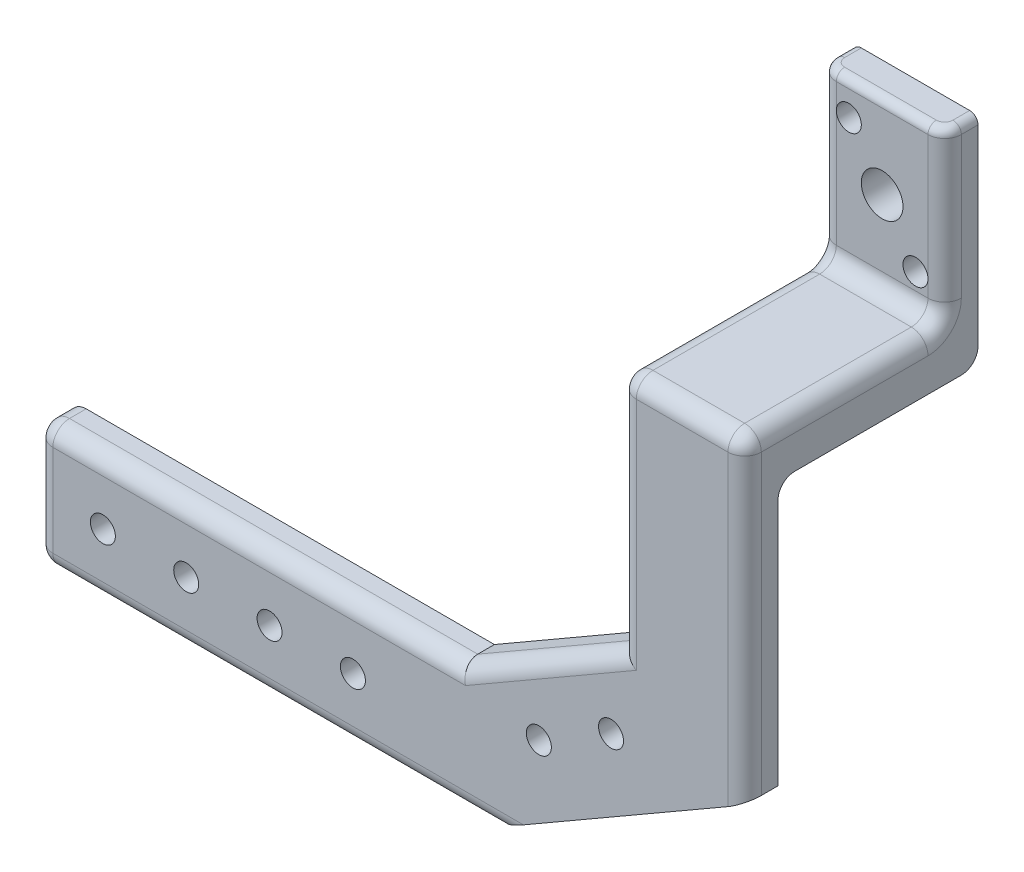
SolidWorks part; units mm, degrees
ref_plane "前视基准面" through (0, 0, 0) normal (0, 0, 1) x (1, 0, 0)
ref_plane "上视基准面" through (0, 0, 0) normal (0, 1, 0) x (1, 0, 0)
ref_plane "右视基准面" through (0, 0, 0) normal (1, 0, 0) x (0, 0, -1)
sketch "草图1" plane through (0, 0, 0) normal (0, 0, 1) x (1, 0, 0)
  line L0 (-7.5, 10) -> (-7.5, -16)
  line L3 (-7.5, 10) -> (7.5, 10)
  line L5 (0, 10) -> (0, -10) construction
  line L6 (-2.5, 0) -> (2.5, 0) construction
  line L9 (-7.5, -16) -> (7.5, -16)
  line L11 (7.5, 10) -> (7.5, -16)
  circle A0 centre (0, 0) radius 2.5
  circle A1 centre (-4, 6) radius 1.5
  circle A2 centre (4, -6) radius 1.5
  point P0 (0, 0)
  dimension "D3" = 5
  dimension "D4" = 3
  dimension "D5" = 3
  dimension "D1" = 26
  dimension "D2" = 15
  dimension "D6" = 4
  dimension "D7" = 4
  dimension "D8" = 6
  dimension "D9" = 6
  dimension "D10" = 15
  dimension "D11" = 10
extrude "凸台-拉伸1" add sketch "草图1" along normal blind 4
sketch "草图14" plane through (0, 0, 4) normal (0, 0, 1) x (1, 0, 0)
  line L1 (-7.5, -16) -> (7.5, -16)
  line L2 (-7.5, -16) -> (-7.5, -10)
  line L3 (-7.5, -10) -> (7.5, -10)
  line L4 (7.5, -16) -> (7.5, -10)
  dimension "D1" = 6
extrude "凸台-拉伸4" add sketch "草图14" along normal blind 20
sketch "草图15" plane through (0, 0, 24) normal (0, 0, 1) x (1, 0, 0)
  line L0 (-7.5, -10) -> (-7.5, -39.0188)
  line L1 (-7.5, -39.0188) -> (-26.52, -50)
  line L2 (-26.52, -50) -> (-77.5, -50)
  line L5 (-77.5, -50) -> (-77.5, -65)
  line L6 (-77.5, -65) -> (-22.5, -65)
  line L8 (-22.5, -65) -> (7.5, -47.6795)
  line L9 (7.5, -47.6795) -> (7.5, -10)
  line L10 (7.5, -10) -> (-7.5, -10)
  line L11 (-7.5, -10) -> (-7.5, -16) construction
  dimension "D1" = 55
  dimension "D2" = 15
  dimension "D3" = 85
  dimension "D4" = 150
  dimension "D5" = 150
  dimension "D6" = 55
  dimension "D7" = 50.98
extrude "凸台-拉伸5" add sketch "草图15" along normal blind 4
sketch "草图17" plane through (0, 0, 24) normal (0, 0, -1) x (-1, 0, 0)
  line L1 (34.5, -52.5) -> (74.5, -52.5)
  line L2 (34.5, -52.5) -> (34.5, -62.5)
  line L3 (34.5, -62.5) -> (74.5, -62.5)
  line L4 (74.5, -52.5) -> (74.5, -62.5)
  line L5 (77.5, -65) -> (22.5, -65) construction
  line L6 (77.5, -50) -> (77.5, -65) construction
  line L7 (26.52, -50) -> (77.5, -50) construction
  dimension "D1" = 2.5
  dimension "D2" = 2.5
  dimension "D3" = 10
  dimension "D4" = 40
  dimension "D5" = 3
extrude "切除-拉伸3" cut sketch "草图17" against normal blind 1.5
sketch "草图18" plane through (0, 0, 25.5) normal (0, 0, -1) x (-1, 0, 0)
  line L0 (74.5, -52.5) -> (34.5, -52.5) construction
  line L1 (34.5, -52.5) -> (34.5, -62.5) construction
  circle A0 centre (39.5, -57.5) radius 1.5
  circle A1 centre (49.5, -57.5) radius 1.5
  circle A2 centre (59.5, -57.5) radius 1.5
  circle A3 centre (69.5, -57.5) radius 1.5
  dimension "D1" = 5
  dimension "D2" = 5
  dimension "D3" = 4
extrude "切除-拉伸4" cut sketch "草图18" against normal blind 2.5
sketch "草图19" plane through (0, 0, 24) normal (0, 0, -1) x (-1, 0, 0)
  line L0 (6.6995, -41.4434) -> (24.02, -51.4434)
  line L1 (24.02, -51.4434) -> (19.02, -60.1036)
  line L2 (19.02, -60.1036) -> (1.6995, -50.1036)
  line L3 (1.6995, -50.1036) -> (6.6995, -41.4434)
  line L6 (7.5, -39.0188) -> (26.52, -50) construction
  dimension "D1" = 2.5
  dimension "D2" = 90
  dimension "D3" = 20
  dimension "D4" = 10
  dimension "D5" = 2.5
extrude "切除-拉伸5" cut sketch "草图19" against normal blind 1.5
sketch "草图20" plane through (0, 0, 25.5) normal (0, 0, -1) x (-1, 0, 0)
  line L0 (6.6995, -41.4434) -> (1.6995, -50.1036) construction
  line L1 (24.02, -51.4434) -> (6.6995, -41.4434) construction
  circle A0 centre (8.5296, -48.2735) radius 1.5
  circle A1 centre (17.1899, -53.2735) radius 1.5
  dimension "D1" = 5
  dimension "D2" = 5
  dimension "D3" = 2
extrude "切除-拉伸6" cut sketch "草图20" against normal blind 2.5
fillet "圆角1" radius 2 16 edges at (7.5, -10, 16) (-7.5, -10, 16) (0, -16, 24) (0, -16, 0) (-50, -65, 28) (-77.5, -65, 26) (-77.5, -50, 26) (-77.5, -57.5, 28) (-52.01, -50, 28) (-17.01, -44.5094, 28) (-7.5, -24.5094, 28) (7.5, -28.8397, 28) (0, -10, 28) (0, -10, 4) (7.5, 0, 4) (-7.5, 0, 4)
fillet "圆角2" radius 1 5 edges at (7.5, 10, 1) (6.9142, 10, 3.4142) (0, 10, 4) (-6.9142, 10, 3.4142) (-7.5, 10, 1)
